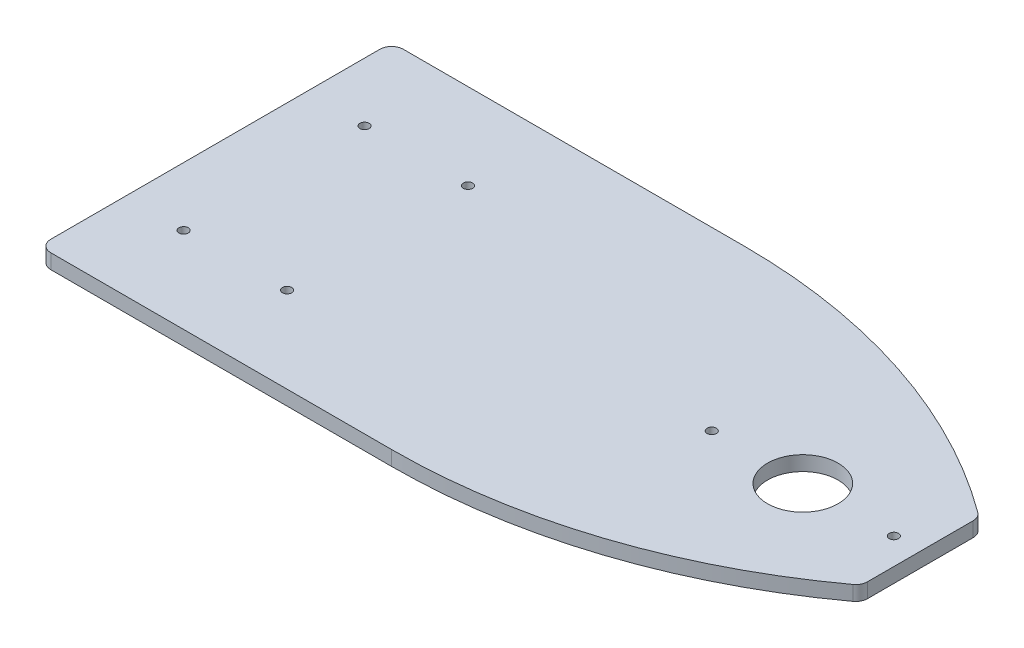
SolidWorks part; units mm, degrees
material "PLA"
ref_plane "Front" through (0, 0, 0) normal (0, 0, 1) x (1, 0, 0)
ref_plane "Top" through (0, 0, 0) normal (0, 1, 0) x (1, 0, 0)
ref_plane "Right" through (0, 0, 0) normal (1, 0, 0) x (0, 0, -1)
sketch "Sketch1" plane through (0, 0, 0) normal (0, 1, 0) x (1, 0, 0)
  line L1 (76.2, -38.1) -> (-76.2, -38.1)
  line L2 (76.2, -38.1) -> (76.2, 38.1)
  line L3 (76.2, 38.1) -> (-76.2, 38.1)
  line L4 (-76.2, -38.1) -> (-76.2, 38.1)
  line L5 (76.2, -38.1) -> (-76.2, 38.1) construction
  line L6 (76.2, 38.1) -> (-76.2, -38.1) construction
  point P0 (0, 0)
  dimension "D1" = 76.2
  dimension "D2" = 152.4
extrude "Boss-Extrude1" add sketch "Sketch1" along normal blind 3.175
sketch "Sketch4" plane through (0, 3.175, 0) normal (0, 1, 0) x (1, 0, 0)
  line L0 (0, 38.1) -> (76.2, 38.1)
  line L1 (76.2, 38.1) -> (-76.2, 38.1) construction
  line L2 (76.2, 38.1) -> (76.2, 12.7)
  line L3 (76.2, -38.1) -> (76.2, 38.1) construction
  line L4 (76.2, -38.1) -> (76.2, -12.7)
  line L5 (76.2, -38.1) -> (0, -38.1)
  line L6 (-76.2, -38.1) -> (76.2, -38.1) construction
  arc A0 (0, -38.1) -> (76.2, -12.7) centre (0, 88.9) ccw
  arc A1 (0, 38.1) -> (76.2, 12.7) centre (0, -88.9) cw
  dimension "D3" = 127
  dimension "D4" = 127
  dimension "D1" = 25.4
  dimension "D2" = 25.4
extrude "Cut-Extrude1" cut sketch "Sketch4" against normal blind 3.175
fillet "Fillet2" radius 2.54 2 edges at (76.2, 1.5875, 12.7) (76.2, 1.5875, -12.7)
fillet "Fillet3" radius 2.54 2 edges at (-76.2, 1.5875, 38.1) (-76.2, 1.5875, -38.1)
sketch "Sketch5" plane through (0, 3.175, 0) normal (0, 1, 0) x (1, 0, 0)
  line L0 (-55, 0) -> (55, 0) construction
  line L1 (76.2, -11.422) -> (76.2, 11.422) construction
  circle A0 centre (50.8, 0) radius 7.62
  dimension "D1" = 15.24
  dimension "D2" = 25.4
extrude "Cut-Extrude2" cut sketch "Sketch5" against normal blind 3.175
sketch "Sketch6" plane through (0, 3.175, 0) normal (0, 1, 0) x (1, 0, 0)
  line L1 (-63.5, 19.558) -> (-63.5, 0)
  line L2 (-63.5, -19.558) -> (-40.128, -19.558)
  line L4 (-24.13, 17.526) -> (-24.13, 16.5227)
  line L5 (-1.7463, 0) -> (1.7463, 0) construction
  line L6 (-63.5, 0) -> (-63.5, -19.558)
  line L7 (-43.815, -19.558) -> (-40.128, -19.558)
  circle A5 centre (-63.5, 19.558) radius 1.0033
  circle A8 centre (-63.5, -19.558) radius 1.0033
  circle A11 centre (-41.1313, -19.558) radius 1.0033
  circle A12 centre (-41.1313, 19.558) radius 1.0033
  dimension "D1" = 19.558
  dimension "D2" = 2.0066
  dimension "D8" = 2.0066
  dimension "D6" = 2.0066
  dimension "D3" = 19.558
sketch "Sketch7" plane through (0, 3.175, 0) normal (0, 1, 0) x (1, 0, 0)
  line L0 (50.8, -7.62) -> (50.8, 7.62)
  line L1 (50.8, 0) -> (70.485, 0)
  line L2 (-1.7463, 0) -> (1.7463, 0) construction
  line L3 (50.8, 0) -> (31.115, 0)
  circle A0 centre (50.8, 0) radius 7.62 construction
  circle A1 centre (70.485, 0) radius 1.0033
  circle A2 centre (31.115, 0) radius 1.0033
  dimension "D3" = 2.0066
  dimension "D4" = 2.0066
  dimension "D1" = 19.685
  dimension "D2" = 19.685
extrude "Cut-Extrude4" cut sketch "Sketch7" against normal through all contours A2 | A1 region at (30.1401, 3.175, 0)
extrude "Cut-Extrude5" cut sketch "Sketch6" against normal through all contours A5 | A8 | L2 A8 L6 | L4 L7 | L7 A11 | L7 A11 | A12 region at (-41.1313, 3.175, 19.1322) region at (-41.1313, 3.175, 19.9838) region at (-63.0742, 3.175, 19.1322) region at (-63.6419, 3.175, 19.6999) region at (-64.1894, 3.175, -20.2474) region at (-41.1313, 3.175, -19.558)
